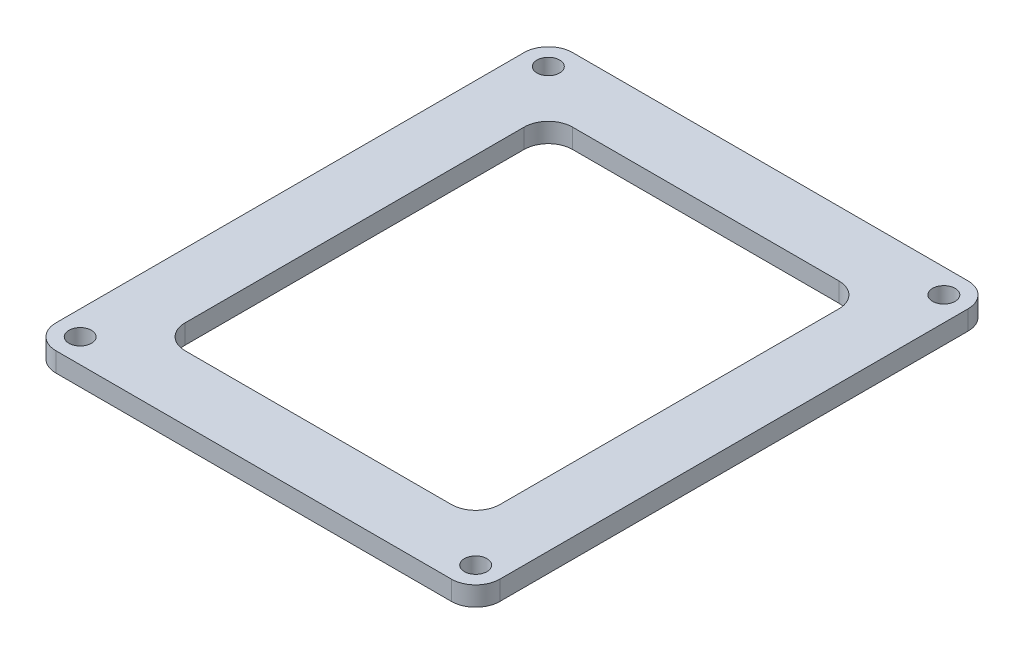
SolidWorks part; units mm, degrees
ref_plane "前视基准面" through (0, 0, 0) normal (0, 0, 1) x (1, 0, 0)
ref_plane "上视基准面" through (0, 0, 0) normal (0, 1, 0) x (1, 0, 0)
ref_plane "右视基准面" through (0, 0, 0) normal (1, 0, 0) x (0, 0, -1)
other "Configuration Table"
sketch "草图1" plane through (0, 0, 0) normal (0, 1, 0) x (1, 0, 0)
  line L0 (0, 46.8686) -> (0, -37.1951) construction
  line L1 (-27.5, -32) -> (27.5, -32)
  line L2 (-27.5, -32) -> (-27.5, 32)
  line L3 (-27.5, 32) -> (27.5, 32)
  line L4 (27.5, -32) -> (27.5, 32)
  line L5 (-27.5, -32) -> (27.5, 32) construction
  line L6 (-27.5, 32) -> (27.5, -32) construction
  line L7 (-32.226, 0) -> (32.7537, 0) construction
  line L8 (-19.5, -24) -> (-19.5, 24)
  line L9 (-19.5, 24) -> (19.5, 24)
  line L10 (19.5, -24) -> (19.5, 24)
  line L11 (-19.5, -24) -> (19.5, -24)
  circle A0 centre (-24.5, 29) radius 1.4
  circle A1 centre (24.5, 29) radius 1.4
  circle A2 centre (24.5, -29) radius 1.4
  circle A3 centre (-24.5, -29) radius 1.4
  point P0 (0, 0)
  dimension "D3" = 2.8
  dimension "D4" = 49
  dimension "D5" = 58
  dimension "D1" = 55
  dimension "D2" = 64
  dimension "D6" = 8
extrude "凸台-拉伸1" add sketch "草图1" along normal blind 2.4
fillet "圆角1" radius 3 8 edges at (-27.5, 1.2, -32) (27.5, 1.2, -32) (27.5, 1.2, 32) (-27.5, 1.2, 32) (-19.5, 1.2, 24) (19.5, 1.2, 24) (19.5, 1.2, -24) (-19.5, 1.2, -24)
